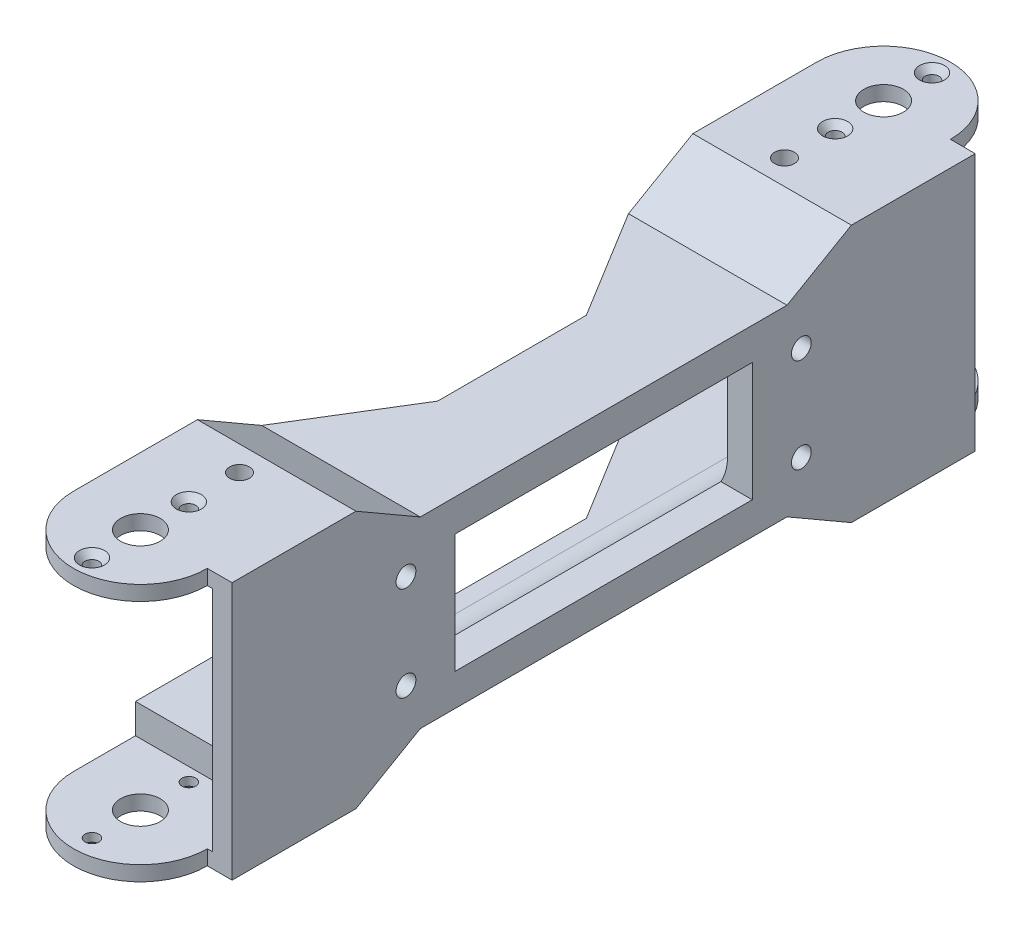
SolidWorks part; units mm, degrees
material "POM Acetal Copolymer"
ref_plane "Front Plane" through (0, 0, 0) normal (0, 0, 1) x (1, 0, 0)
ref_plane "Top Plane" through (0, 0, 0) normal (0, 1, 0) x (1, 0, 0)
ref_plane "Right Plane" through (0, 0, 0) normal (1, 0, 0) x (0, 0, -1)
sketch "Sketch1" plane through (0, 0, 0) normal (0, 1, 0) x (1, 0, 0)
  line L0 (0, 75) -> (0, -75) construction
  line L2 (-13.5, 75) -> (-13.5, -75)
  line L4 (13.5, 75) -> (13.5, -75)
  arc A0 (13.5, 75) -> (-13.5, 75) centre (0, 75) ccw
  arc A1 (-13.5, -75) -> (13.5, -75) centre (0, -75) ccw
  circle A2 centre (0, -55) radius 2
  point P5 (0, 0)
  dimension "D3" = 4
  dimension "D1" = 150
  dimension "D2" = 27
  dimension "D4" = 20
extrude "Boss-Extrude1" add sketch "Sketch1" along normal mid plane 52
sketch "Sketch3" plane through (-13.5, 0, 0) normal (-1, 0, 0) x (0, 0, 1)
  line L0 (-50, 26) -> (-37.0096, 18.5)
  line L1 (-75, 26) -> (75, 26) construction
  line L2 (-37.0096, 18.5) -> (37.0096, 18.5)
  line L3 (37.0096, 18.5) -> (50, 26)
  line L4 (50, 26) -> (-50, 26)
  line L5 (-75, 26) -> (-75, -26) construction
  point P6 (0, 18.5)
  point P7 (0, 26)
  dimension "D1" = 7.5
  dimension "D2" = 30
  dimension "D3" = 25
extrude "Cut-Extrude1" cut sketch "Sketch3" against normal through all both and the other way through all
mirror "Mirror1" about plane through (0, 0, 0) normal (0, 1, 0) of "Cut-Extrude1"
sketch "Sketch4" plane through (-13.5, 0, 0) normal (-1, 0, 0) x (0, 0, 1)
  line L0 (-88.5, 26) -> (-88.5, -26) construction
  line L1 (62.5, 23) -> (88.5, 23)
  line L2 (-88.5, 23) -> (-62.5, 23)
  line L3 (-88.5, 23) -> (-88.5, 17)
  line L4 (-88.5, 17) -> (-62.5, 17)
  line L5 (-62.5, 23) -> (-62.5, 17)
  line L6 (-88.5, -23) -> (-62.5, -23)
  line L7 (-88.5, -23) -> (-88.5, -17)
  line L8 (-88.5, -17) -> (-62.5, -17)
  line L9 (-62.5, -23) -> (-62.5, -17)
  line L10 (62.5, 23) -> (62.5, 17)
  line L11 (62.5, 17) -> (88.5, 17)
  line L12 (88.5, 23) -> (88.5, 17)
  line L13 (62.5, -17) -> (88.5, -17)
  line L14 (62.5, -17) -> (62.5, -23)
  line L15 (62.5, -23) -> (88.5, -23)
  line L16 (88.5, -17) -> (88.5, -23)
  line L18 (88.5, -26) -> (88.5, 26) construction
  line L19 (-62.5, 17) -> (-62.5, -17) construction
  line L20 (62.5, 17) -> (62.5, -17) construction
  point P20 (-62.5, 0)
  dimension "D1" = 26
  dimension "D2" = 6
  dimension "D3" = 34
extrude "Cut-Extrude2" cut sketch "Sketch4" against normal through all both
sketch "Sketch5" plane through (-13.5, 0, 0) normal (-1, 0, 0) x (0, 0, 1)
  line L1 (-88.5, 17) -> (88.5, 17)
  line L2 (-88.5, 17) -> (-88.5, -17)
  line L3 (-88.5, -17) -> (88.5, -17)
  line L4 (88.5, 17) -> (88.5, -17)
extrude "Cut-Extrude3" cut sketch "Sketch5" against normal offset from surface (22 mm away) 5 up to face at (13.5, 0, 0)
sketch "Sketch6" plane through (8.5, 0, 0) normal (-1, 0, 0) x (0, 0, 1)
  line L0 (62.5, -17) -> (-62.5, -17) construction
  line L1 (85.4881, 17) -> (62.5, 17)
  line L2 (85.4881, 17) -> (85.4881, -17)
  line L3 (85.4881, -17) -> (62.5, -17)
  line L4 (62.5, 17) -> (62.5, -17)
  line L5 (62.5, -17) -> (62.5, -23) construction
extrude "Cut-Extrude4" cut sketch "Sketch6" against normal through all
sketch "Sketch7" plane through (8.5, 0, 0) normal (-1, 0, 0) x (0, 0, 1)
  line L1 (-85.4881, 17) -> (-62.5, 17)
  line L2 (-85.4881, 17) -> (-85.4881, -17)
  line L3 (-85.4881, -17) -> (-62.5, -17)
  line L4 (-62.5, 17) -> (-62.5, -17)
extrude "Cut-Extrude5" cut sketch "Sketch7" against normal through all
hole_wizard "CSK for #3 Flat Head Machine Screw1" positions "Sketch11" profile "Sketch12" countersink size "#3" standard "ANSI Inch"
sketch "Sketch11" plane through (0, 26, 0) normal (0, 1, 0) x (1, 0, 0)
  line L0 (9.779, -75) -> (-9.779, -75) construction
  line L2 (0, -65.221) -> (0, -84.779) construction
  arc A0 (-13.5, -75) -> (13.5, -75) centre (0, -75) ccw construction
  point P0 (0, -65.221)
  point P6 (0, -84.779)
  point P17 (0, -75)
  point P18 (0, -75)
  dimension "D1" = 19.558
sketch "Sketch12" plane through (0, 26, 65.221) normal (1, 0, 0) x (0, 0, 1)
  line L0 (0, 0) -> (0, 3.8394)
  line L1 (0, 3.8394) -> (1.397, 3)
  line L2 (1.397, 3) -> (1.397, 1.3003)
  line L3 (1.397, 1.3003) -> (2.5273, 0)
  line L5 (2.5273, 0) -> (0, 0)
  line L6 (-1.397, 1.3003) -> (-2.5273, 0) construction
  line L10 (0, 3.8394) -> (-1.397, 3) construction
  line L11 (0, -6.35) -> (0, 107.95) construction
  dimension "Hole Dia." = 2.794
  dimension "Hole Depth" = 3
  dimension "Near C'Sink Dia." = 5.0546
  dimension "Near C'Sink Angle" = 82
  dimension "Drill Angle" = 118
mirror "Mirror5" about plane through (0, 0, 0) normal (0, 1, 0) of "CSK for #3 Flat Head Machine Screw1"
mirror "Mirror3" about plane through (0, 0, 0) normal (0, 0, 1) of "CSK for #3 Flat Head Machine Screw1"
sketch "Sketch13" plane through (0, -26, 0) normal (0, -1, 0) x (1, 0, 0)
  circle A0 centre (0, -75) radius 4
  arc A1 (-13.5, -75) -> (13.5, -75) centre (0, -75) ccw construction
  dimension "D1" = 8
extrude "Cut-Extrude6" cut sketch "Sketch13" against normal through all both and the other way through all
mirror "Mirror4" about plane through (0, 0, 0) normal (0, 0, 1) of "Cut-Extrude6"
sketch "Sketch14" plane through (13.5, 0, 0) normal (1, 0, 0) x (0, 0, -1)
  line L0 (-75, 26) -> (-75, 23)
  line L1 (-75, 23) -> (-62.5, 23)
  line L2 (-62.5, 23) -> (-62.5, -23)
  line L3 (-62.5, -23) -> (-75, -23)
  line L4 (-75, -23) -> (-75, -26)
  line L5 (-75, -26) -> (-50, -26)
  line L6 (-50, -26) -> (-37.0096, -18.5)
  line L7 (-37.0096, -18.5) -> (37.0096, -18.5)
  line L8 (37.0096, -18.5) -> (50, -26)
  line L12 (62.5, -23) -> (62.5, 23)
  line L13 (62.5, 23) -> (75, 23)
  line L14 (75, 23) -> (75, 26)
  line L15 (75, 26) -> (50, 26)
  line L16 (50, 26) -> (37.0096, 18.5)
  line L17 (37.0096, 18.5) -> (-37.0096, 18.5)
  line L18 (-37.0096, 18.5) -> (-50, 26)
  line L19 (-50, 26) -> (-75, 26)
  line L20 (62.5, -23) -> (75, -23)
  line L21 (75, -23) -> (75, -26)
  line L22 (75, -26) -> (50, -26)
extrude "Boss-Extrude2" add sketch "Sketch14" along normal blind 5
sketch "Sketch15" plane through (8.5, 0, 0) normal (-1, 0, 0) x (0, 0, 1)
  line L1 (-62.5, 17) -> (62.5, 17)
  line L2 (-62.5, 17) -> (-62.5, -17)
  line L3 (-62.5, -17) -> (62.5, -17)
  line L4 (62.5, 17) -> (62.5, -17)
extrude "Cut-Extrude7" cut sketch "Sketch15" against normal blind 5
sketch "Sketch17" plane through (0, 0, 62.5) normal (0, 0, 1) x (1, 0, 0)
  line L0 (18.5, -26) -> (13.5, -26) construction
  line L1 (18.5, 26) -> (14.5, 26)
  line L2 (18.5, 26) -> (18.5, -26)
  line L3 (18.5, -26) -> (14.5, -26)
  line L4 (14.5, 26) -> (14.5, -26)
  dimension "D1" = 4
extrude "Boss-Extrude4" add sketch "Sketch17" along normal up to surface (12.5 mm away) up to face at (16, 24.5, 75)
mirror "Mirror6" about plane through (0, 0, 0) normal (0, 1, 0) of "Mirror3"
sketch "Sketch19" plane through (18.5, 0, 0) normal (1, 0, 0) x (0, 0, -1)
  line L0 (-39.899, 9.525) -> (-39.899, -9.525) construction
  line L3 (-75, 26) -> (-75, -26) construction
  circle A0 centre (-39.899, 9.525) radius 2
  circle A1 centre (-39.899, -9.525) radius 2
  point P4 (-39.899, 0)
  dimension "D2" = 4
  dimension "D1" = 19.05
  dimension "D3" = 35.101
extrude "Cut-Extrude11" cut sketch "Sketch19" against normal blind 10
sketch "Sketch18" plane through (0, 26, 0) normal (0, 1, 0) x (1, 0, 0)
  circle A0 centre (0, 55) radius 2
  circle A2 centre (0, 75) radius 4 construction
  dimension "D1" = 4
  dimension "D2" = 20
extrude "Cut-Extrude8" cut sketch "Sketch18" against normal up to surface (52 mm away) up to face at (0, -26, -67.7483)
sketch "Sketch20" plane through (13.5, 0, 0) normal (-1, 0, 0) x (0, 0, 1)
  line L1 (-30, 12) -> (30, 12)
  line L2 (-30, 12) -> (-30, -12)
  line L3 (-30, -12) -> (30, -12)
  line L4 (30, 12) -> (30, -12)
  point P4 (30, 0)
  point P8 (0, -12)
  dimension "D1" = 60
  dimension "D2" = 24
extrude "Cut-Extrude10" cut sketch "Sketch20" against normal blind 10
mirror "Mirror7" about plane through (0, 0, 0) normal (0, 0, 1) of "Cut-Extrude11"
sketch "Sketch21" plane through (0, 18.5, 0) normal (0, 1, 0) x (1, 0, 0)
  line L0 (-13.5, 37.0096) -> (0, 15)
  line L2 (0, 15) -> (0, -15)
  line L3 (0, -15) -> (-13.5, -37.0096)
  line L4 (-13.5, -37.0096) -> (-13.5, 37.0096)
  line L5 (18.5, 37.0096) -> (-13.5, 37.0096) construction
  point P4 (-13.5, 0)
  point P9 (0, 0)
  dimension "D1" = 30
extrude "Cut-Extrude12" cut sketch "Sketch21" against normal up to surface (37 mm away)
sketch "Sketch22" plane through (0, 0, -62.5) normal (0, 0, -1) x (-1, 0, 0)
  line L1 (-18.5, 23) -> (-13.5, 23)
  line L2 (-18.5, 23) -> (-18.5, -23)
  line L3 (-18.5, -23) -> (-13.5, -23)
  line L4 (-13.5, 23) -> (-13.5, -23)
extrude "Boss-Extrude5" add sketch "Sketch22" along normal up to surface (12.5 mm away) up to face at (16, 24.5, -75)
fillet "Fillet1" radius 10 2 edges at (13.5, 17, 0) (13.5, -17, 0)
